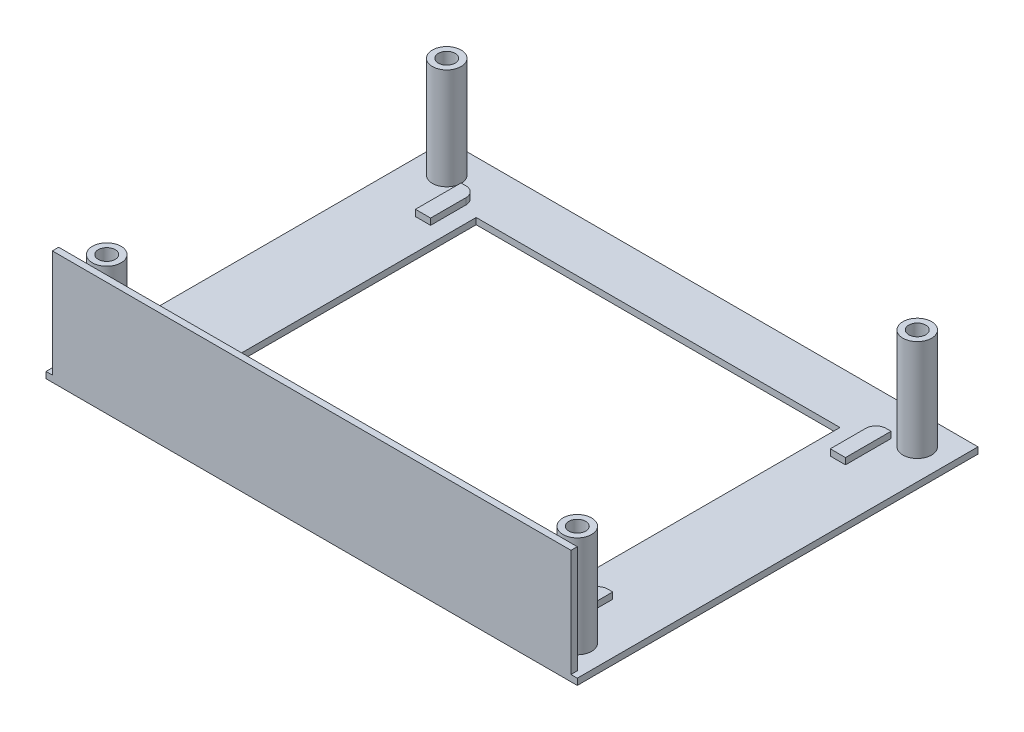
SolidWorks part; units mm, degrees
ref_plane "Front Plane" through (0, 0, 0) normal (0, 0, 1) x (1, 0, 0)
ref_plane "Top Plane" through (0, 0, 0) normal (0, 1, 0) x (1, 0, 0)
ref_plane "Right Plane" through (0, 0, 0) normal (1, 0, 0) x (0, 0, -1)
sketch "Sketch1" plane through (0, 0, 0) normal (0, 1, 0) x (1, 0, 0)
  line L1 (-45.6406, -34.1312) -> (45.6406, -34.1312)
  line L2 (-45.6406, -34.1312) -> (-45.6406, 34.1313)
  line L3 (-45.6406, 34.1313) -> (45.6406, 34.1313)
  line L4 (45.6406, -34.1312) -> (45.6406, 34.1313)
  line L5 (-45.6406, -34.1312) -> (45.6406, 34.1313) construction
  line L6 (-45.6406, 34.1313) -> (45.6406, -34.1312) construction
  line L7 (-49.6406, 38.1313) -> (50.6406, 38.1313)
  line L8 (-49.6406, 35.5913) -> (-49.6406, -43.1312)
  line L9 (-49.6406, -43.1312) -> (50.6406, -43.1312)
  line L10 (50.6406, -34.2413) -> (50.6406, -43.1312)
  line L11 (19.6844, -43.1312) -> (-7.5719, -43.1312)
  line L12 (19.6844, -43.1312) -> (19.6844, -49.4812)
  line L13 (19.6844, -49.4812) -> (-7.5719, -49.4812)
  line L14 (-7.5719, -43.1312) -> (-7.5719, -49.4812)
  line L15 (-66.1506, 47.2512) -> (67.1506, 47.2512)
  line L16 (-66.1506, 47.2512) -> (-66.1506, -53.2912)
  line L17 (-66.1506, -53.2912) -> (67.1506, -53.2912)
  line L18 (67.1506, 47.2512) -> (67.1506, -53.2912)
  line L19 (-52.1806, 38.1313) -> (-53.4506, 38.1313)
  line L20 (-49.6406, 38.1313) -> (-49.6406, 26.7013)
  line L21 (-49.6406, 26.7013) -> (-53.4506, 26.7013)
  line L22 (-53.4506, 38.1313) -> (-53.4506, 26.7013)
  line L23 (53.1806, 38.1313) -> (54.4506, 38.1313)
  line L24 (50.6406, 38.1313) -> (50.6406, 26.7013)
  line L25 (50.6406, 26.7013) -> (54.4506, 26.7013)
  line L26 (54.4506, 38.1313) -> (54.4506, 26.7013)
  line L27 (-49.6406, -43.1312) -> (-53.4506, -43.1312)
  line L28 (-49.6406, -43.1312) -> (-49.6406, -34.2413)
  line L29 (-52.1806, -31.7012) -> (-53.4506, -31.7012)
  line L30 (-53.4506, -43.1312) -> (-53.4506, -31.7012)
  line L31 (50.6406, -43.1312) -> (54.4506, -43.1312)
  line L32 (50.6406, -43.1312) -> (50.6406, -31.7012)
  line L33 (53.1806, -31.7012) -> (54.4506, -31.7012)
  line L34 (54.4506, -43.1312) -> (54.4506, -31.7012)
  line L35 (-53.4506, -46.9412) -> (-36.9406, -46.9412)
  line L36 (-53.4506, -46.9412) -> (-53.4506, -43.1312)
  line L37 (-53.4506, -43.1312) -> (-36.9406, -43.1312)
  line L38 (-36.9406, -46.9412) -> (-36.9406, -43.1312)
  line L39 (54.4506, -43.1312) -> (39.2106, -43.1312)
  line L40 (54.4506, -43.1312) -> (54.4506, -46.9412)
  line L41 (54.4506, -46.9412) -> (39.2106, -46.9412)
  line L42 (39.2106, -43.1312) -> (39.2106, -46.9412)
  line L43 (-66.1506, -53.2912) -> (67.1506, -53.2912)
  line L44 (-66.1506, -53.2912) -> (-66.1506, -51.7038)
  line L45 (-66.1506, -51.7038) -> (67.1506, -51.7038)
  line L46 (67.1506, -53.2912) -> (67.1506, -51.7038)
  line L47 (-66.1506, -51.7038) -> (-64.5631, -51.7038)
  line L48 (-66.1506, -51.7038) -> (-66.1506, -53.2912)
  line L49 (-66.1506, -53.2912) -> (-64.5631, -53.2913)
  line L50 (-64.5631, -51.7038) -> (-64.5631, -53.2913)
  line L51 (67.1506, -51.7038) -> (65.5631, -51.7038)
  line L52 (67.1506, -51.7038) -> (67.1506, -53.2912)
  line L53 (67.1506, -53.2912) -> (65.5631, -53.2913)
  line L54 (65.5631, -51.7038) -> (65.5631, -53.2913)
  arc A0 (-49.6406, 35.5913) -> (-52.1806, 38.1313) centre (-52.1806, 35.5913) ccw
  arc A1 (50.6406, 35.5912) -> (53.1806, 38.1313) centre (53.1806, 35.5913) cw
  arc A2 (50.6406, -34.2413) -> (53.1806, -31.7012) centre (53.1806, -34.2412) cw
  arc A3 (-49.6406, -34.2413) -> (-52.1806, -31.7012) centre (-52.1806, -34.2412) ccw
  circle A4 centre (59.5306, 39.6312) radius 3.6
  circle A5 centre (-58.5306, 39.6312) radius 3.6
  circle A6 centre (59.5306, -45.6712) radius 3.6
  circle A7 centre (-58.5306, -45.6713) radius 3.6
  circle A8 centre (-58.5306, 39.6312) radius 2.125
  circle A9 centre (59.5306, 39.6312) radius 2.125
  circle A10 centre (59.5306, -45.6712) radius 2.125
  circle A11 centre (-58.5306, -45.6713) radius 2.125
  point P0 (0, 0)
  point P14 (0, 0)
  point P48 (-49.6406, -31.7012)
  dimension "D24" = 2.54
  dimension "D25" = 2.54
  dimension "D20" = 2.54
  dimension "D26" = 2.54
  dimension "D27" = 7.62
  dimension "D35" = 1.5875
  dimension "D1" = 91.2812
  dimension "D2" = 68.2625
  dimension "D3" = 4
  dimension "D4" = 4
  dimension "D5" = 5
  dimension "D6" = 9
  dimension "D7" = 30.9562
  dimension "D8" = 42.0688
  dimension "D9" = 6.35
  dimension "D10" = 16.51
  dimension "D11" = 16.51
  dimension "D12" = 3.81
  dimension "D13" = 11.43
  dimension "D14" = 3.81
  dimension "D15" = 3.81
  dimension "D16" = 11.43
  dimension "D17" = 3.81
  dimension "D18" = 16.51
  dimension "D19" = 3.81
  dimension "D21" = 11.43
  dimension "D22" = 11.43
  dimension "D23" = 3.81
  dimension "D28" = 7.62
  dimension "D29" = 7.62
  dimension "D30" = 7.62
  dimension "D31" = 7.62
  dimension "D32" = 7.62
  dimension "D33" = 7.62
  dimension "D34" = 7.62
  dimension "D36" = 1.5875
  dimension "D37" = 1.5875
extrude "Boss-Extrude1" add sketch "Sketch1" against normal blind 1.5875 contours L17 L18 L15 L16
extrude "Boss-Extrude2" add sketch "Sketch1<3>" along normal blind 25.4 contours A5 A8 | A4 A9 | A6 A10 | A7 A11 region at (56.0324, 0, -39.6312) region at (-62.0288, 0, -39.6312) region at (56.0324, 0, 45.6712) region at (-62.0288, 0, 45.6713)
sketch "Sketch1<3>" plane through (0, 0, 0) normal (0, 1, 0) x (1, 0, 0) same geometry as "Sketch1"
extrude "Boss-Extrude4" add sketch "Sketch1<6>" along normal blind 1.5875 contours L8 A0 L19 L22 L21 | A1 L24 L25 L26 L23 | A2 L10 L31 L34 L33 | L9 L42 L41 L40 L31 | L35 L38 L9 L27 L36 | L8 A3 L29 L30 L27 region at (52.5895, 0, -32.2472) region at (46.8306, 0, 45.0362) region at (-51.5895, 0, 37.5853) region at (-51.5895, 0, -32.2472) region at (-45.1956, 0, 45.0362) region at (52.5895, 0, 37.5853)
sketch "Sketch1<6>" plane through (0, 0, 0) normal (0, 1, 0) x (1, 0, 0) same geometry as "Sketch1"
extrude "Cut-Extrude1" cut sketch "Sketch1<7>" against normal blind 4.1275 contours L1 L4 L3 L2 region at (0, 0, 0)
sketch "Sketch1<7>" plane through (0, 0, 0) normal (0, 1, 0) x (1, 0, 0) same geometry as "Sketch1"
extrude "Boss-Extrude5" add sketch "Sketch1<9>" along normal blind 26.9875 contours L54 L45 L50 L43 region at (0.5, 0, 52.4975)
sketch "Sketch1<9>" plane through (0, 0, 0) normal (0, 1, 0) x (1, 0, 0) same geometry as "Sketch1"
